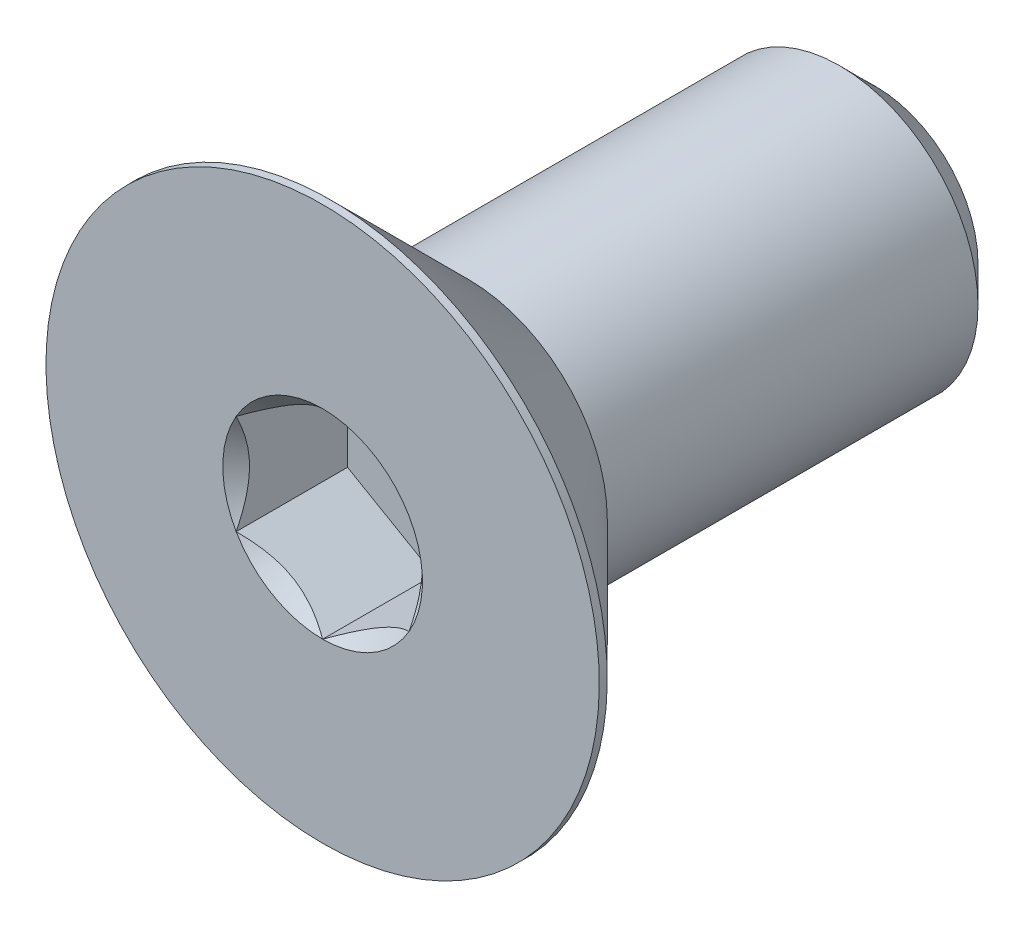
SolidWorks part; units mm, degrees
material "1.4310 (X10CrNi18-8)"
ref_plane "Front" through (0, 0, 0) normal (0, 0, 1) x (1, 0, 0)
ref_plane "Top" through (0, 0, 0) normal (0, 1, 0) x (1, 0, 0)
ref_plane "Right" through (0, 0, 0) normal (1, 0, 0) x (0, 0, -1)
sketch "Sketch11" plane through (0, 0, 0) normal (1, 0, 0) x (0, 0, -1)
  line L0 (-4, 4) -> (4, 4) construction
  line L5 (-4, 4) -> (-4, -4) construction
  line L6 (4, 2) -> (4, -2) construction
  line L7 (-3.99, 1.25) -> (-3.99, -1.25) construction
  line L8 (3.9562, 2.0758) -> (4.6563, 2.0758) construction
  line L9 (4.6563, 2.0758) -> (4.3062, 1.4696) construction
  line L10 (4.3062, 1.4696) -> (3.9562, 2.0758) construction
  line L11 (4.2625, 1.5453) -> (4.35, 1.5453) construction
  line L12 (4.3062, 1.5453) -> (4.3062, 1.4696) construction
  line L13 (3.9781, 2.0379) -> (4.6344, 2.0379) construction
  line L14 (4.3062, 2.0758) -> (4.3062, 2) construction
  line L15 (4, 2) -> (4.6125, 2) construction
  line L17 (-3.885, 4) -> (0.115, 0) construction
  line L18 (0.115, 0) -> (-3.885, -4) construction
  point P3 (-1.7, 4)
  point P8 (0, 4)
  point P21 (4.3062, 2.0379)
  point P26 (-4, 0)
  point P28 (-3.99, 0)
  point P29 (4, 0)
  dimension "Length" = 8
  dimension "Head Diameter" = 8
  dimension "Thread Major Diameter" = 4
  dimension "Head Height" = 2.3
  dimension "Drive Size" = 2.5
  dimension "Thread Pitch" = 0.7
  dimension "D1" = 0.0875
  dimension "D2" = 0.01
  dimension "D3" = 0.115
  dimension "Countersink Angle" = 90
sketch "Sketch1" plane through (0, 0, 0) normal (1, 0, 0) x (0, 0, -1)
  line L2 (-1.7, 2) -> (4, 2)
  line L3 (4, 2) -> (4, 0)
  line L4 (-2.39, 2) -> (-2.39, 0)
  line L5 (-1.7, 2) -> (-2.39, 2)
  line L6 (-4, 4) -> (-4, -4) construction
  line L7 (4, 2) -> (4, -2) construction
  line L8 (-2.39, 0) -> (4, 0)
  dimension "D1" = 1.61
revolve "Revolve1" add sketch "Sketch1" angle 360 mid plane about L8
chamfer "Chamfer1" distance 0.525 angle 45 1 edges at (0, -2, -4)
sketch "Sketch7" plane through (0, 0, 0) normal (1, 0, 0) x (0, 0, -1)
  line L2 (-4, 4) -> (-3.885, 4)
  line L5 (-1.7, 1.815) -> (-1.7, 0)
  line L6 (-4, 4) -> (-4, 0)
  line L8 (-4, 4) -> (-4, -4) construction
  line L9 (-4, 0) -> (-1.7, 0)
  line L12 (-3.885, 4) -> (-1.7, 1.815)
  line L13 (-3.885, 4) -> (0.115, 0) construction
revolve "Revolve2" add sketch "Sketch7" angle 360 mid plane about L9 region at (0, 1.5544, 2.9977)
ref_plane "Plane1" through (0, 0, 1.7) normal (0, 0, 1) x (1, 0, 0)
sketch "Sketch5" plane through (0, 0, 4) normal (0, 0, 1) x (1, 0, 0)
  line L1 (1.25, -0.7217) -> (1.25, 0.7217)
  line L2 (1.25, 0.7217) -> (0, 1.4434)
  line L3 (0, 1.4434) -> (-1.25, 0.7217)
  line L4 (-1.25, 0.7217) -> (-1.25, -0.7217)
  line L5 (-1.25, -0.7217) -> (0, -1.4434)
  line L6 (0, -1.4434) -> (1.25, -0.7217)
  circle A0 centre (0, 0) radius 1.25 construction
extrude "Cut-Extrude2" cut sketch "Sketch5" against normal blind 1.61
sketch "Sketch6" plane through (0, 0, 4) normal (0, 0, -1) x (-1, 0, 0)
  circle A0 centre (0, 0) radius 1.4434
extrude "Cut-Extrude3" cut sketch "Sketch6" along normal blind 1.61 draft 45
sketch "Sketch12" plane through (0, 0, -4) normal (0, 0, -1) x (-1, 0, 0)
  circle A0 centre (0, 0) radius 2 construction
  circle A1 centre (0, 0) radius 2
curve "Helix/Spiral1" pitch 0.7 height 8 turns 11.4286
sketch "Sketch13" plane through (0, 0, 0) normal (1, 0, 0) x (0, 0, -1)
  line L0 (3.9781, 2.0379) -> (4.6344, 2.0379)
  line L1 (4.6344, 2.0379) -> (4.35, 1.5453)
  line L2 (4.35, 1.5453) -> (4.2625, 1.5453)
  line L3 (4.2625, 1.5453) -> (3.9781, 2.0379)
sweep "Cut-Sweep1" [suppressed] cut profiles "Sketch13" path "Helix/Spiral1"
combine bodies "Combine1" operation type add bodies to combine 113 108
equation "\"D1@Chamfer1\"=\"Thread Pitch@Sketch11\" * .75"
equation "\"D1@Cut-Extrude2\"= \"Head Height@Sketch11\" * .7"
equation "\"D1@Cut-Extrude3\" = \"D1@Cut-Extrude2\""
equation "\"D1@Sketch11\"=\"Thread Pitch@Sketch11\"/8"
equation "\"D3@Sketch11\"=\"Head Height@Sketch11\"*.05"
equation "\"D4@Helix/Spiral1\"=\"Thread Pitch@Sketch11\""
equation "\"D1@Sketch1\"=\"Head Height@Sketch11\"*.7"
equation "\"D3@Helix/Spiral1\"=\"Length@Sketch11\""
